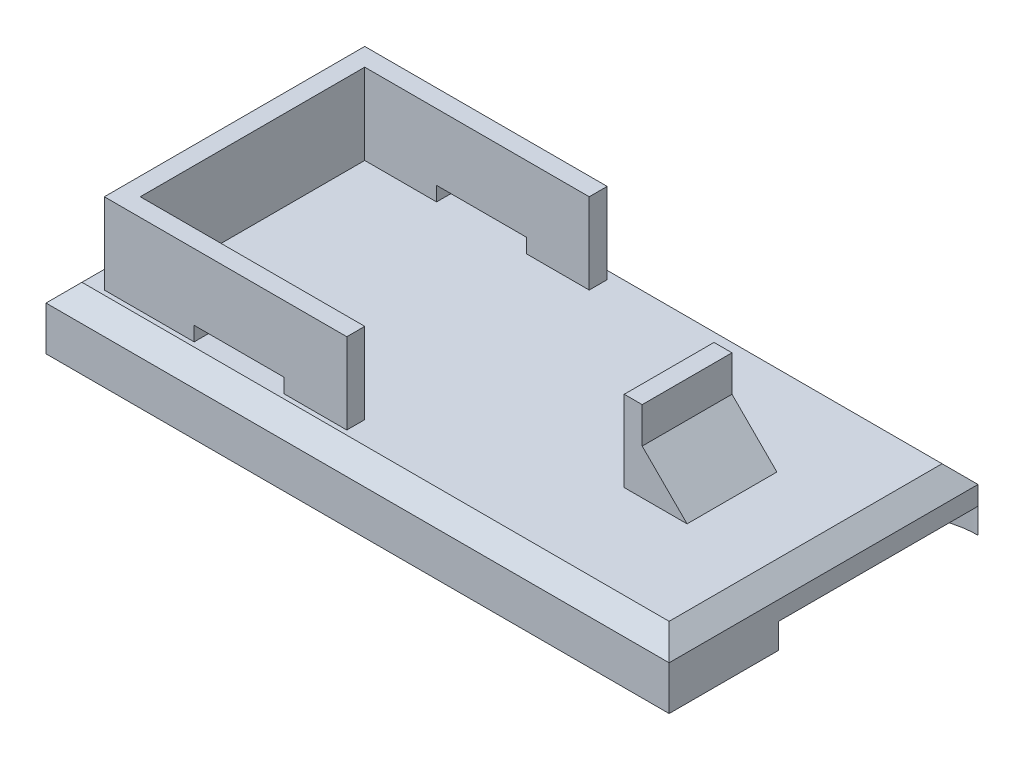
SolidWorks part; units mm, degrees
ref_plane "Front Plane" through (0, 0, 0) normal (0, 0, 1) x (1, 0, 0)
ref_plane "Top Plane" through (0, 0, 0) normal (0, 1, 0) x (1, 0, 0)
ref_plane "Right Plane" through (0, 0, 0) normal (1, 0, 0) x (0, 0, -1)
sketch "Sketch1" plane through (0, 0, 0) normal (0, 1, 0) x (1, 0, 0)
  line L1 (-42.9471, 32.3009) -> (45.1909, 32.3009)
  line L2 (-42.9471, 32.3009) -> (-42.9471, -11.3871)
  line L3 (-42.9471, -11.3871) -> (45.1909, -11.3871)
  line L4 (45.1909, 32.3009) -> (45.1909, -11.3871)
  dimension "D1" = 88.138
  dimension "D2" = 43.688
extrude "Boss-Extrude1" add sketch "Sketch1" along normal blind 8.763
chamfer "Chamfer1" distance 2.54 angle 45 4 edges at (-42.9471, 8.763, -10.4569) (1.1219, 8.763, -32.3009) (45.1909, 8.763, -10.4569) (1.1219, 8.763, 11.3871)
sketch "Sketch2" plane through (0, 8.763, 0) normal (0, 1, 0) x (1, 0, 0)
  line L30 (-40.4071, -8.8471) -> (42.6509, -8.8471) construction
  line L31 (-37.8671, 28.6179) -> (-35.3271, 28.6179)
  line L32 (-37.8671, 28.6179) -> (-37.8671, -8.2121)
  line L33 (-37.8671, -8.2121) -> (-35.3271, -8.2121)
  line L34 (-35.3271, 26.0779) -> (-35.3271, -5.6721)
  line L35 (-35.3271, -8.2121) -> (-3.5771, -8.2121)
  line L37 (-35.3271, -5.6721) -> (-3.5771, -5.6721)
  line L38 (-3.5771, -8.2121) -> (-3.5771, -5.6721)
  line L39 (-35.3271, 28.6179) -> (-3.5771, 28.6179)
  line L41 (-35.3271, 26.0779) -> (-3.5771, 26.0779)
  line L42 (-3.5771, 28.6179) -> (-3.5771, 26.0779)
  line L43 (-40.4071, 29.7609) -> (-40.4071, -8.8471) construction
  line L44 (42.6509, 29.7609) -> (-40.4071, 29.7609) construction
  line L45 (23.0929, 17.0609) -> (25.6329, 17.0609)
  line L46 (23.0929, 17.0609) -> (23.0929, 4.3609)
  line L47 (23.0929, 4.3609) -> (25.6329, 4.3609)
  line L48 (25.6329, 17.0609) -> (25.6329, 4.3609)
  dimension "D1" = 36.83
  dimension "D2" = 2.54
  dimension "D3" = 0.635
  dimension "D4" = 2.54
  dimension "D5" = 2.54
  dimension "D6" = 2.54
  dimension "D7" = 31.75
  dimension "D8" = 31.75
  dimension "D9" = 12.7
  dimension "D10" = 2.54
  dimension "D11" = 12.7
  dimension "D12" = 58.42
extrude "Boss-Extrude2" add sketch "Sketch2" along normal blind 11.43
sketch "Sketch3" plane through (-37.8671, 0, 0) normal (-1, 0, 0) x (0, 0, 1)
  line L5 (-32.3009, 0) -> (11.3871, 0) construction
  line L6 (-19.7279, 7.8105) -> (0.5921, 7.8105)
  line L7 (-19.7279, 7.8105) -> (-19.7279, 4.0005)
  line L8 (-19.7279, 4.0005) -> (0.5921, 4.0005)
  line L9 (0.5921, 7.8105) -> (0.5921, 4.0005)
  line L10 (-28.6179, 20.193) -> (-28.6179, 8.763) construction
  dimension "D1" = 4.0005
  dimension "D2" = 20.32
  dimension "D3" = 8.89
  dimension "D4" = 3.81
extrude "Boss-Extrude3" add sketch "Sketch3" along normal blind 7.62
chamfer "Chamfer2" distance 2.54 angle 45 1 edges at (-45.4871, 4.0005, -9.5679)
sketch "Sketch4" plane through (0, 0, 8.2121) normal (0, 0, 1) x (1, 0, 0)
  line L0 (-37.8671, 8.763) -> (-3.5771, 8.763) construction
  line L1 (-25.1671, 8.763) -> (-12.4671, 8.763)
  line L2 (-25.1671, 8.763) -> (-25.1671, 10.795)
  line L3 (-25.1671, 10.795) -> (-12.4671, 10.795)
  line L4 (-12.4671, 8.763) -> (-12.4671, 10.795)
  line L5 (-3.5771, 20.193) -> (-3.5771, 8.763) construction
  dimension "D1" = 12.7
  dimension "D2" = 2.032
  dimension "D3" = 8.89
extrude "Cut-Extrude1" cut sketch "Sketch4" against normal blind 50.8
sketch "Sketch5" plane through (0, 0, 0) normal (0, -1, 0) x (1, 0, 0)
  line L0 (45.1909, -10.4569) -> (-42.9471, -10.4569) construction
  line L1 (45.1909, 11.3871) -> (45.1909, -32.3009) construction
  line L2 (-42.9471, -32.3009) -> (-42.9471, 11.3871) construction
  line L3 (35.0309, -4.1069) -> (45.1909, -4.1069)
  line L4 (45.1909, -4.1069) -> (45.1909, -16.8069)
  line L6 (45.1909, -16.8069) -> (45.1909, -32.3009)
  arc A0 (35.0309, -4.1069) -> (28.6809, -10.4569) centre (35.0309, -10.4569) ccw
  ellipse E0 centre (45.1909, -10.4569) end of major axis (45.1909, -32.3009) minor radius 16.51 (28.6809, -10.4569) -> (45.1909, -32.3009) ccw
  dimension "D1" = 12.7
  dimension "D2" = 10.16
extrude "Cut-Extrude2" cut sketch "Sketch5" against normal blind 3.556
chamfer "Chamfer3" distance 6.35 angle 45 1 edges at (25.6329, 8.763, -10.7109)
